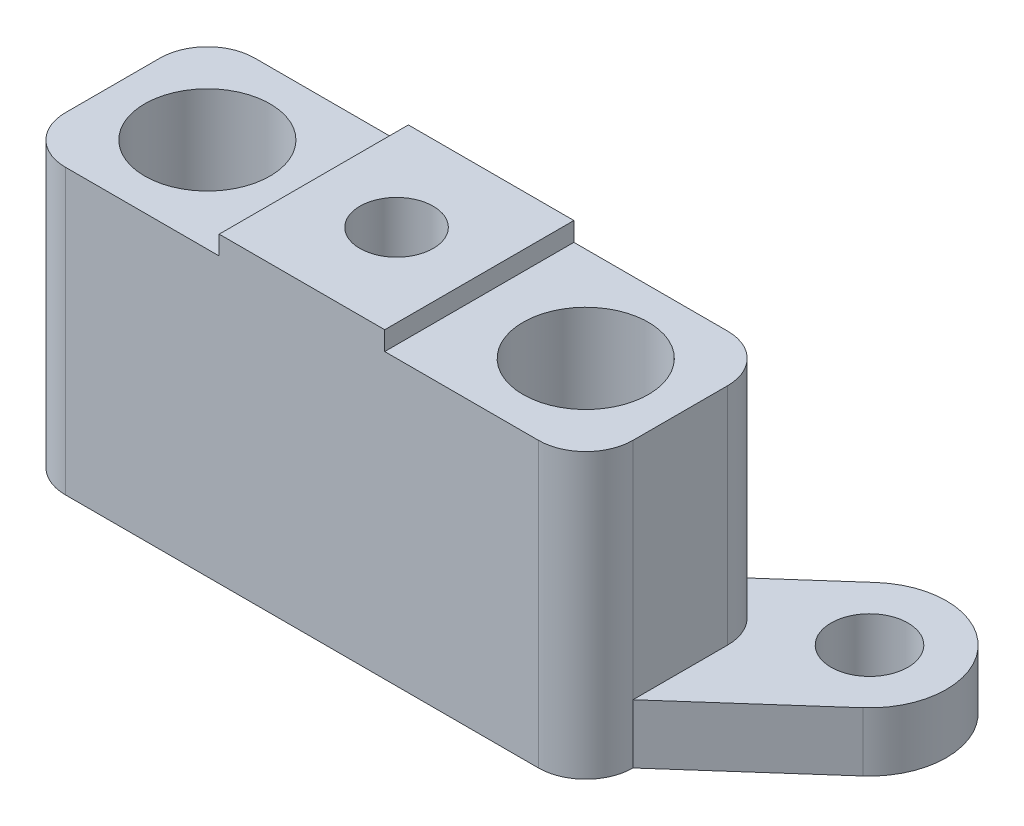
SolidWorks part; units mm, degrees
ref_plane "Front Plane" through (0, 0, 0) normal (0, 0, 1) x (1, 0, 0)
ref_plane "Top Plane" through (0, 0, 0) normal (0, 1, 0) x (1, 0, 0)
ref_plane "Right Plane" through (0, 0, 0) normal (1, 0, 0) x (0, 0, -1)
ref_axis "X-Axis" through (-88.4377, 0, 0) along (1, 0, 0)
ref_axis "Y-Axis" through (0, 0, -69.2525) along (0, 0, 1)
ref_axis "Z-Axis" through (0, -52.5493, 0) along (0, 1, 0)
sketch "Sketch25" plane through (0, 0, 0) normal (0, 1, 0) x (-1, 0, 0)
  line L8 (3.5, -4) -> (-3.5, -4)
  line L9 (3.5, -4) -> (3.5, 4)
  line L10 (3.5, 4) -> (-3.5, 4)
  line L11 (-3.5, -4) -> (-3.5, 4)
  line L12 (3.5, -4) -> (-3.5, 4) construction
  line L13 (3.5, 4) -> (-3.5, -4) construction
  point P8 (0, 0)
  dimension "D3" = 7
  dimension "D1" = 8
extrude "Boss-Extrude5" add sketch "Sketch25" along normal blind 12.8
sketch "Sketch26" plane through (0, 0, 0) normal (0, 1, 0) x (-1, 0, 0)
  line L0 (0, 4) -> (0, -4) construction
  line L1 (-12, -4) -> (12, -4)
  line L2 (-12, -4) -> (-12, 4)
  line L3 (-12, 4) -> (12, 4)
  line L4 (12, -4) -> (12, 4)
  line L5 (-12, 0) -> (12, 0) construction
  line L6 (-8, 0) -> (0, -4) construction
  line L7 (0, -4) -> (8, 0) construction
  line L10 (-3.5, -4) -> (3.5, -4) construction
  line L11 (3.5, 4) -> (-3.5, 4) construction
  circle A0 centre (-8, 0) radius 2.65
  circle A1 centre (8, 0) radius 2.65
  dimension "D2" = 5.3
  dimension "D1" = 24
  dimension "D3" = 16
extrude "Boss-Extrude6" add sketch "Sketch26" along normal blind 12
fillet "Fillet1" radius 2 4 edges at (12, 6, -4) (-12, 6, -4) (-12, 6, 4) (12, 6, 4)
sketch "Sketch27" plane through (0, 12.8, 0) normal (0, 1, 0) x (1, 0, 0)
  circle A0 centre (0, 0) radius 1.55
  dimension "D1" = 3.1
extrude "Cut-Extrude1" cut sketch "Sketch27" against normal blind 6.5
ref_plane "Plane1" through (0, 0, 0) normal (0, -1, 0) x (-1, 0, 0)
sketch "Sketch29" plane through (0, 0, 0) normal (0, -1, 0) x (1, 0, 0)
  line L0 (0, 0) -> (0, 33) construction
  line L1 (0, 33) -> (-15, 33) construction
  line L2 (-15, 33) -> (-15, -5) construction
  line L3 (-17.1552, -2.5674) -> (-12, 2)
  line L4 (-12.8448, -7.4326) -> (-8.9704, -4)
  line L5 (10, -4) -> (-10, -4) construction
  line L6 (-12, 2) -> (-11, -3)
  line L7 (-11, -3) -> (-8.9704, -4)
  line L8 (17.1552, -2.5674) -> (12, 2)
  line L9 (12, 2) -> (11, -3)
  line L10 (11, -3) -> (8.9704, -4)
  line L11 (12.8448, -7.4326) -> (8.9704, -4)
  circle A0 centre (-15, -5) radius 1.625
  arc A1 (-17.1552, -2.5674) -> (-12.8448, -7.4326) centre (-15, -5) ccw
  circle A2 centre (15, -5) radius 1.625
  arc A3 (17.1552, -2.5674) -> (12.8448, -7.4326) centre (15, -5) cw
  dimension "D4" = 3.25
  dimension "D5" = 6.5
  dimension "D1" = 33
  dimension "D2" = 38
  dimension "D3" = 15
extrude "Boss-Extrude8" add sketch "Sketch29" against normal blind 2.5
